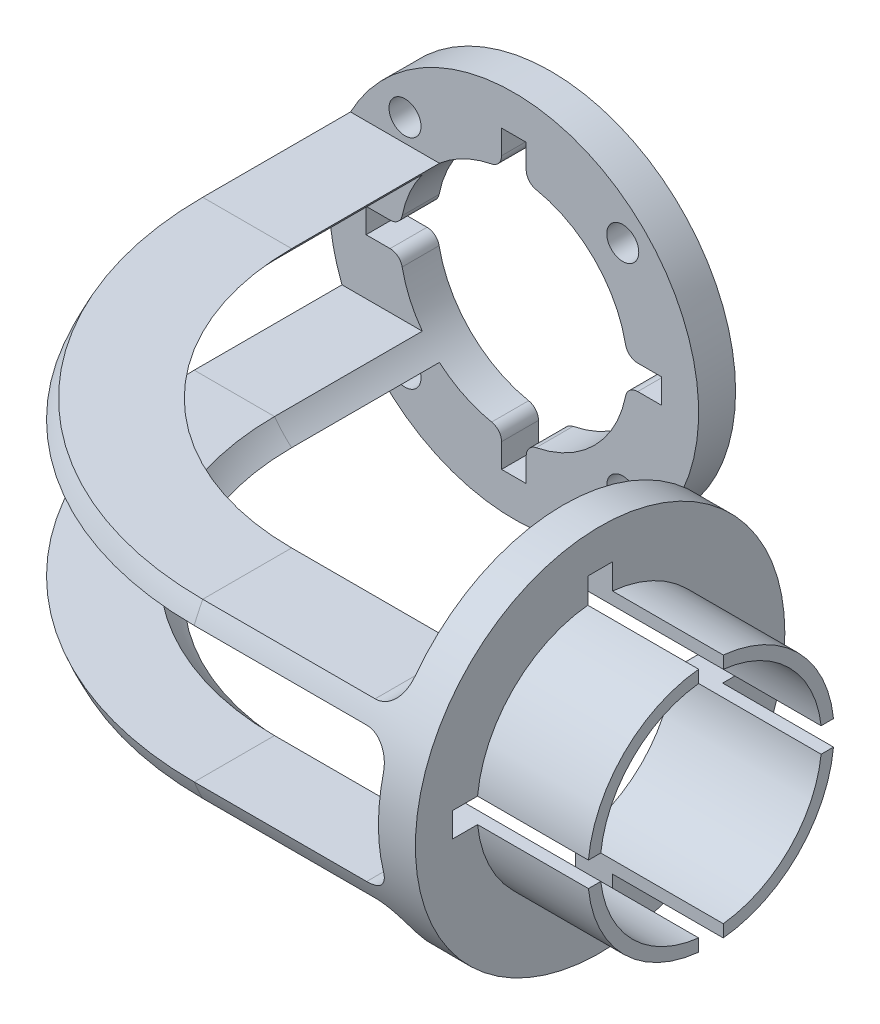
SolidWorks part; units mm, degrees
material "尼龙 101"
ref_plane "前视基准面" through (0, 0, 0) normal (0, 0, 1) x (1, 0, 0)
ref_plane "上视基准面" through (0, 0, 0) normal (0, 1, 0) x (1, 0, 0)
ref_plane "右视基准面" through (0, 0, 0) normal (1, 0, 0) x (0, 0, -1)
sketch "草图1" plane through (0, 0, 0) normal (0, 0, 1) x (1, 0, 0)
  circle A0 centre (0, 0) radius 9.25
  circle A1 centre (0, 0) radius 15
  dimension "D1" = 18.5
  dimension "D2" = 30
extrude "凸台-拉伸1" add sketch "草图1" along normal blind 3
sketch "草图2" plane through (0, 0, 3) normal (0, 0, 1) x (1, 0, 0)
  line L0 (0, 0) -> (0, 15) construction
  line L1 (-1, 9.1958) -> (-1, 12)
  line L2 (-1, 12) -> (1, 12)
  line L3 (1, 12) -> (1, 9.1958)
  line L4 (0, 0) -> (-19.1322, 0) construction
  line L5 (-1, -9.1958) -> (-1, -12)
  line L6 (1, -12) -> (1, -9.1958)
  line L7 (-1, -12) -> (1, -12)
  line L8 (-9.1958, 1) -> (-12, 1)
  line L9 (-12, 1) -> (-12, -1)
  line L10 (-12, -1) -> (-9.1958, -1)
  line L11 (9.1958, 1) -> (12, 1)
  line L12 (12, 1) -> (12, -1)
  line L13 (12, -1) -> (9.1958, -1)
  circle A0 centre (0, 0) radius 15 construction
  circle A1 centre (0, 0) radius 9.25 construction
  arc A2 (9.1958, -1) -> (9.1958, 1) centre (0, 0) ccw
  arc A3 (1, 9.1958) -> (-1, 9.1958) centre (0, 0) ccw
  arc A4 (-9.1958, 1) -> (-9.1958, -1) centre (0, 0) ccw
  arc A5 (-1, -9.1958) -> (1, -9.1958) centre (0, 0) ccw
  dimension "D1" = 2
  dimension "D2" = 24
  dimension "D3" = 2
  dimension "D4" = 24
extrude "切除-拉伸1" cut sketch "草图2" against normal through all
fillet "圆角1" radius 1 8 edges at (1, -9.1958, 1.5) (-1, -9.1958, 1.5) (-9.1958, -1, 1.5) (9.1958, -1, 1.5) (9.1958, 1, 1.5) (-9.1958, 1, 1.5) (1, 9.1958, 1.5) (-1, 9.1958, 1.5)
sketch "草图3" plane through (0, 0, 3) normal (0, 0, 1) x (1, 0, 0)
  line L0 (0, 0) -> (12.5, 0) construction
  line L1 (0, 0) -> (8.8388, 8.8388) construction
  circle A0 centre (0, 0) radius 12.5 construction
  circle A1 centre (8.8388, 8.8388) radius 1.3
  circle A2 centre (8.8388, -8.8388) radius 1.3
  circle A3 centre (-8.8388, -8.8388) radius 1.3
  circle A4 centre (-8.8388, 8.8388) radius 1.3
  point P15 (0, 0)
  dimension "D1" = 25
  dimension "D3" = 2.6
  dimension "D2" = 45
  dimension "D4" = 4
extrude "切除-拉伸2" cut sketch "草图3" against normal through all
sketch "草图5" plane through (0, 0, 3) normal (0, 0, 1) x (1, 0, 0)
  line L0 (-13.2665, 7) -> (-6.0467, 7)
  line L1 (-13.9553, 5.5) -> (-7.4372, 5.5)
  line L2 (0, 0) -> (-25.2397, 0) construction
  line L3 (-13.2665, -7) -> (-6.0467, -7)
  line L4 (-13.9553, -5.5) -> (-7.4372, -5.5)
  circle A0 centre (0, 0) radius 15 construction
  arc A1 (-1.8049, 9.0722) -> (-9.0722, 1.8049) centre (0, 0) ccw construction
  arc A2 (-13.2665, 7) -> (-13.9553, 5.5) centre (0, 0) ccw
  arc A3 (-6.0467, 7) -> (-7.4372, 5.5) centre (0, 0) ccw
  arc A4 (-6.0467, -7) -> (-7.4372, -5.5) centre (0, 0) cw
  arc A5 (-13.2665, -7) -> (-13.9553, -5.5) centre (0, 0) cw
  dimension "D1" = 1.5
  dimension "D2" = 5.5
sketch "草图6" plane through (0, 0, 0) normal (0, 1, 0) x (1, 0, 0)
  line L0 (0, -3) -> (0, -15)
  line L1 (-15, -3) -> (15, -3) construction
  line L2 (34, -30) -> (15, -30)
  arc A0 (15, -30) -> (0, -15) centre (15, -15) cw
  point P11 (0, -30)
  dimension "D1" = 15
sweep "扫描1" add profiles "草图5" path "草图6"
sketch "草图7" plane through (34, 0, 0) normal (1, 0, 0) x (0, 0, -1)
  line L0 (-29, -8.9443) -> (-29, -12)
  line L1 (-29, -12) -> (-31, -12)
  line L2 (-31, -12) -> (-31, -8.9443)
  line L3 (-38.9443, -1) -> (-42, -1)
  line L4 (-42, -1) -> (-42, 1)
  line L5 (-42, 1) -> (-38.9443, 1)
  line L6 (-29, 8.9443) -> (-29, 12)
  line L7 (-29, 12) -> (-31, 12)
  line L8 (-31, 12) -> (-31, 8.9443)
  line L9 (-21.0557, -1) -> (-18, -1)
  line L10 (-18, -1) -> (-18, 1)
  line L11 (-18, 1) -> (-21.0557, 1)
  arc A0 (-31, 8.9443) -> (-38.9443, 1) centre (-30, 0) ccw
  circle A1 centre (-30, 0) radius 15
  arc A2 (-21.0557, 1) -> (-29, 8.9443) centre (-30, 0) ccw
  arc A3 (-29, -8.9443) -> (-21.0557, -1) centre (-30, 0) ccw
  arc A4 (-38.9443, -1) -> (-31, -8.9443) centre (-30, 0) ccw
  dimension "D1" = 18
  dimension "D2" = 30
extrude "凸台-拉伸2" add sketch "草图7" against normal blind 3
sketch "草图8" plane through (34, 0, 0) normal (1, 0, 0) x (0, 0, -1)
  line L0 (-31, -8.9443) -> (-31, -12) construction
  line L1 (-29, -12) -> (-29, -8.9443) construction
  line L2 (-31, -8.9443) -> (-31, -9.9499)
  line L3 (-29, -9.9499) -> (-29, -8.9443)
  line L4 (-42, -1) -> (-38.9443, -1) construction
  line L5 (-38.9443, 1) -> (-42, 1) construction
  line L6 (-18, 1) -> (-21.0557, 1) construction
  line L7 (-21.0557, -1) -> (-18, -1) construction
  line L8 (-39.9499, -1) -> (-38.9443, -1)
  line L9 (-38.9443, 1) -> (-39.9499, 1)
  line L10 (-20.0501, 1) -> (-21.0557, 1)
  line L11 (-21.0557, -1) -> (-20.0501, -1)
  line L12 (-31, 12) -> (-31, 8.9443) construction
  line L13 (-29, 8.9443) -> (-29, 12) construction
  line L14 (-31, 9.9499) -> (-31, 8.9443)
  line L15 (-29, 8.9443) -> (-29, 9.9499)
  arc A0 (-21.0557, 1) -> (-29, 8.9443) centre (-30, 0) ccw
  arc A1 (-20.0501, 1) -> (-29, 9.9499) centre (-30, 0) ccw
  arc A2 (-31, 8.9443) -> (-38.9443, 1) centre (-30, 0) ccw
  arc A3 (-31, 9.9499) -> (-39.9499, 1) centre (-30, 0) ccw
  arc A4 (-38.9443, -1) -> (-31, -8.9443) centre (-30, 0) ccw
  arc A5 (-39.9499, -1) -> (-31, -9.9499) centre (-30, 0) ccw
  arc A6 (-29, -8.9443) -> (-21.0557, -1) centre (-30, 0) ccw
  arc A7 (-29, -9.9499) -> (-20.0501, -1) centre (-30, 0) ccw
  dimension "D2" = 20
extrude "凸台-拉伸3" add sketch "草图8" along normal blind 9
fillet "圆角2" radius 1 2 edges at (31, 6.2886, 36.7836) (31, -6.2886, 36.7836)
fillet "圆角3" radius 2 4 edges at (31, -7, 39.4617) (31, -5.5, 40.5396) (31, 5.5, 40.5396) (31, 7, 39.4617)
